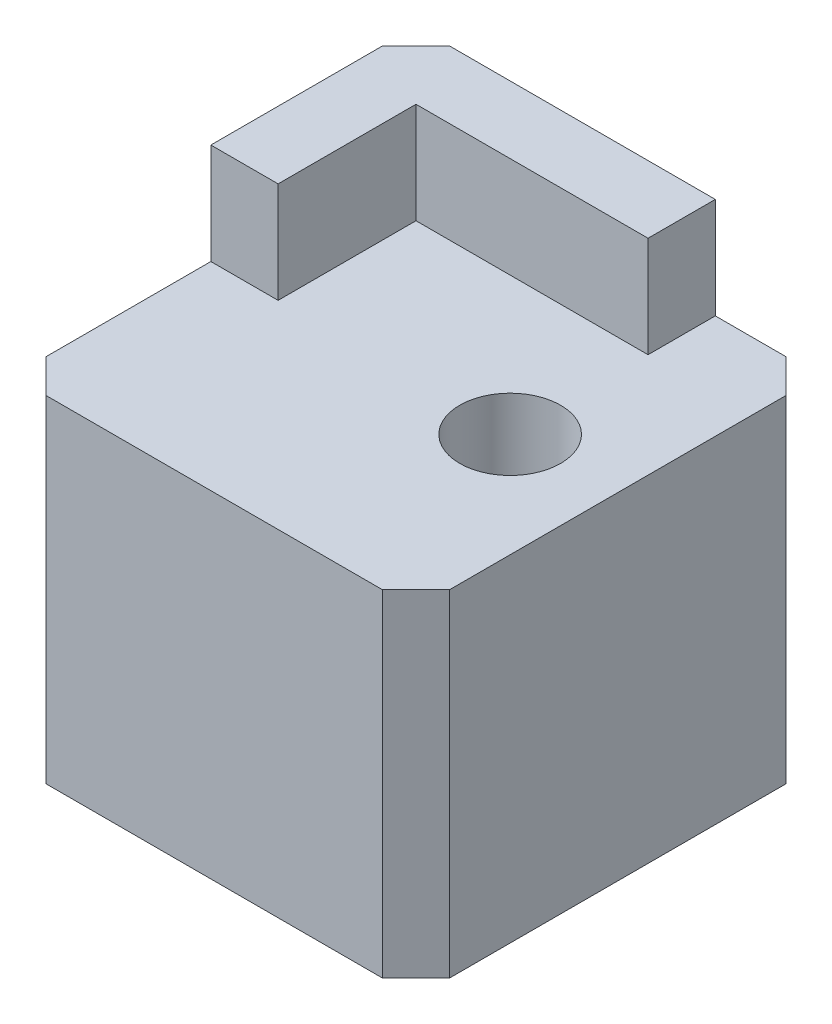
SolidWorks part; units mm, degrees
ref_plane "Front Plane" through (0, 0, 0) normal (0, 0, 1) x (1, 0, 0)
ref_plane "Top Plane" through (0, 0, 0) normal (0, 1, 0) x (1, 0, 0)
ref_plane "Right Plane" through (0, 0, 0) normal (1, 0, 0) x (0, 0, -1)
sketch "Sketch1" plane through (0, 0, 0) normal (0, 1, 0) x (1, 0, 0)
  line L0 (0, 4.1) -> (-6.9, 4.1)
  line L1 (-6.9, 4.1) -> (-6.9, 0)
  line L2 (-6.9, 0) -> (-8.9, 0)
  line L3 (-8.9, 0) -> (-8.9, 6.1)
  line L4 (-8.9, 6.1) -> (0, 6.1)
  line L5 (0, 6.1) -> (0, 4.1)
  line L7 (-8.9, 6.1) -> (3.1, 6.1)
  line L8 (-8.9, 6.1) -> (-8.9, -5.9)
  line L9 (-8.9, -5.9) -> (3.1, -5.9)
  line L10 (3.1, 6.1) -> (3.1, -5.9)
  circle A0 centre (0, 0) radius 1.5
  dimension "D1" = 3
  dimension "D2" = 6.9
  dimension "D3" = 4.1
  dimension "D4" = 2
  dimension "D5" = 12
extrude "Boss-Extrude1" add sketch "Sketch1" against normal blind 10 contours L7 L10 L9 L8
extrude "Boss-Extrude2" add sketch "Sketch1<3>" along normal blind 3 contours L5 L4 L3 L2 L1 L0 region at (-5.5381, 0, -4.1381)
sketch "Sketch1<3>" plane through (0, 0, 0) normal (0, 1, 0) x (1, 0, 0) same geometry as "Sketch1"
chamfer "Chamfer1" distance 1 angle 45 4 edges at (-8.9, -3.5, -6.1) (3.1, -5, -6.1) (-8.9, -5, 5.9) (3.1, -5, 5.9)
extrude "Cut-Extrude1" cut sketch "Sketch1<4>" against normal through all contours A0 region at (0, 0, 0)
sketch "Sketch1<4>" plane through (0, 0, 0) normal (0, 1, 0) x (1, 0, 0) same geometry as "Sketch1"
cosmetic thread "Cosmetic Thread1" parameters "D2"=4
